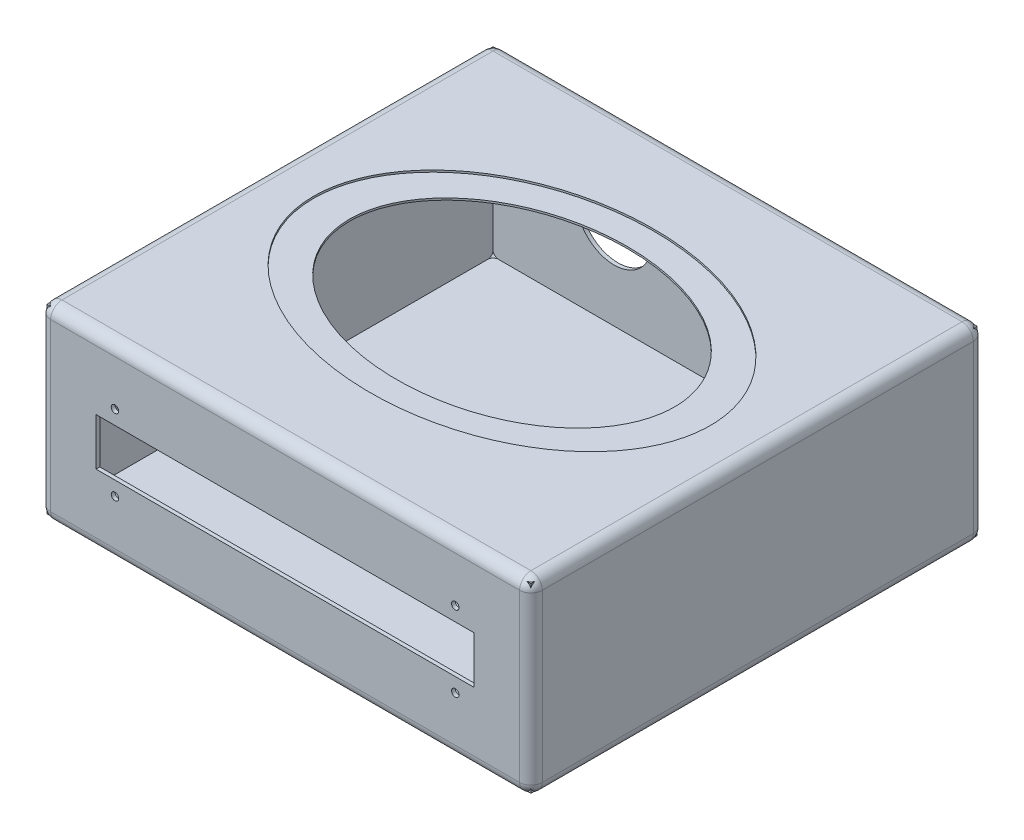
SolidWorks part; units mm, degrees
ref_plane "Front Plane" through (0, 0, 0) normal (0, 0, 1) x (1, 0, 0)
ref_plane "Top Plane" through (0, 0, 0) normal (0, 1, 0) x (1, 0, 0)
ref_plane "Right Plane" through (0, 0, 0) normal (1, 0, 0) x (0, 0, -1)
sketch "Sketch1" plane through (0, 0, 0) normal (0, 1, 0) x (1, 0, 0)
  line L5 (-165.1, -152.4) -> (165.1, -152.4)
  line L6 (-165.1, -152.4) -> (-165.1, 152.4)
  line L7 (-165.1, 152.4) -> (165.1, 152.4)
  line L8 (165.1, -152.4) -> (165.1, 152.4)
  line L9 (-165.1, -152.4) -> (165.1, 152.4) construction
  line L10 (-165.1, 152.4) -> (165.1, -152.4) construction
  point P0 (0, 0)
  dimension "D1" = 330.2
  dimension "D2" = 304.8
extrude "Boss-Extrude1" add sketch "Sketch1" along normal blind 127
shell "Shell1" thickness 2.54
fillet "Fillet1" radius 7.62 12 edges at (165.1, 0, 0) (-165.1, 0, 0) (165.1, 127, 0) (-165.1, 127, 0) (165.1, 63.5, 152.4) (165.1, 63.5, -152.4) (-165.1, 63.5, -152.4) (-165.1, 63.5, 152.4) (0, 0, -152.4) (0, 0, 152.4) (0, 127, 152.4) (0, 127, -152.4)
sketch "Sketch2" plane through (0, 0, -152.4) normal (0, 0, -1) x (-1, 0, 0)
  line L0 (157.48, 7.62) -> (157.48, 119.38) construction
  line L1 (-157.48, 0) -> (157.48, 0) construction
  circle A0 centre (81.28, 63.5) radius 25.4
  dimension "D1" = 50.8
  dimension "D2" = 76.2
  dimension "D3" = 63.5
extrude "Cut-Extrude1" cut sketch "Sketch2" against normal blind 25.4
sketch "Sketch3" plane through (0, 0, -152.4) normal (0, 0, -1) x (-1, 0, 0)
  line L5 (-165.1, 7.62) -> (-165.1, 119.38) construction
  line L6 (-157.48, 0) -> (157.48, 0) construction
  circle A0 centre (-127, 50.8) radius 11
  dimension "D1" = 22
  dimension "D2" = 38.1
  dimension "D3" = 50.8
extrude "Cut-Extrude2" cut sketch "Sketch3" against normal blind 25.4
sketch "Sketch4" plane through (0, 0, 152.4) normal (0, 0, 1) x (1, 0, 0)
  line L1 (-127, 47.625) -> (127, 47.625)
  line L2 (-127, 47.625) -> (-127, 79.375)
  line L3 (-127, 79.375) -> (127, 79.375)
  line L4 (127, 47.625) -> (127, 79.375)
  line L5 (0, 79.375) -> (0, 47.625) construction
  line L6 (-127, 63.5) -> (127, 63.5) construction
  line L7 (-157.48, 0) -> (157.48, 0) construction
  line L8 (165.1, 119.38) -> (165.1, 7.62) construction
  point P0 (0, 63.5)
  dimension "D1" = 254
  dimension "D2" = 31.75
  dimension "D3" = 63.5
  dimension "D4" = 165.1
extrude "Cut-Extrude3" cut sketch "Sketch4" against normal blind 25.4
sketch "Sketch5" plane through (0, 127, 0) normal (0, 1, 0) x (1, 0, 0)
  line L1 (-157.48, -152.4) -> (157.48, -152.4) construction
  ellipse E0 centre (0, 0) end of major axis (-109.22, 0) minor radius 77.47
  dimension "D1" = 218.44
  dimension "D3" = 77.47
  dimension "D5" = 74.93
extrude "Cut-Extrude4" cut sketch "Sketch5" against normal blind 25.4
sketch "Sketch6" plane through (0, 127, 0) normal (0, 1, 0) x (1, 0, 0)
  line L0 (-157.48, -152.4) -> (157.48, -152.4) construction
  ellipse E0 centre (0, 0) end of major axis (-133.35, 0) minor radius 95.25
  dimension "D1" = 95.25
  dimension "D2" = 266.7
  dimension "D3" = 57.15
extrude "Cut-Extrude5" cut sketch "Sketch6" against normal blind 1.27
sketch "Sketch7" plane through (0, 0, 152.4) normal (0, 0, 1) x (1, 0, 0)
  line L0 (-127, 79.375) -> (-127, 47.625) construction
  line L1 (127, 79.375) -> (-127, 79.375) construction
  circle A0 centre (-114.3, 88.9) radius 2.5
  point P4 (-127, 63.5)
  point P7 (0, 79.375)
  dimension "D1" = 5
  dimension "D2" = 25.4
  dimension "D3" = 114.3
extrude "Cut-Extrude6" cut sketch "Sketch7" against normal blind 2.54
pattern_linear "LPattern1" count 2 spacing 228.6 along (1, 0, 0) count 2 spacing 50.8 along (0, -1, 0) of "Cut-Extrude6"
